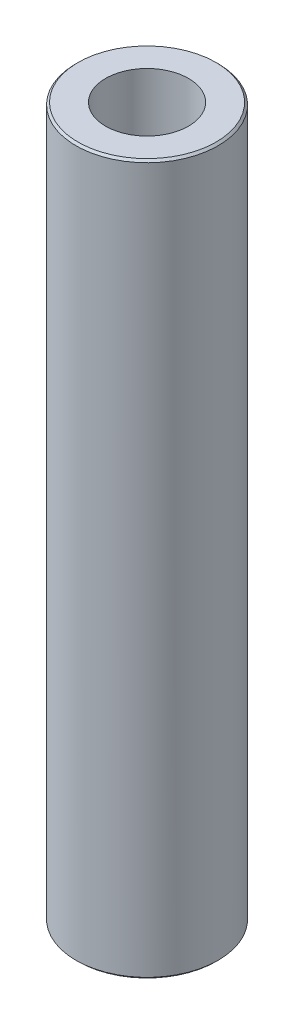
SolidWorks part; units mm, degrees
ref_plane "Front Plane" through (0, 0, 0) normal (0, 0, 1) x (1, 0, 0)
ref_plane "Top Plane" through (0, 0, 0) normal (0, 1, 0) x (1, 0, 0)
ref_plane "Right Plane" through (0, 0, 0) normal (1, 0, 0) x (0, 0, -1)
sketch "Sketch1" plane through (0, 0, 0) normal (0, 1, 0) x (1, 0, 0)
  circle A0 centre (0, 0) radius 27.5
  dimension "SHAFT_OD" = 55
extrude "Boss-Extrude1" add sketch "Sketch1" along normal blind 274.5118
sketch "Sketch2" plane through (0, 0, 0) normal (0, 1, 0) x (1, 0, 0)
  circle A0 centre (0, 0) radius 16.0297
  dimension "BORE_D" = 32.0593
extrude "Cut-Extrude1" cut sketch "Sketch2" along normal through all
chamfer "Chamfer1" distance 0.8167 angle 44.621 2 edges at (0, 274.5118, 27.5) (0, 0, 27.5) first distance on face at (0, 274.5118, 27.5) first distance on face at (0, 0, 16.0297)
